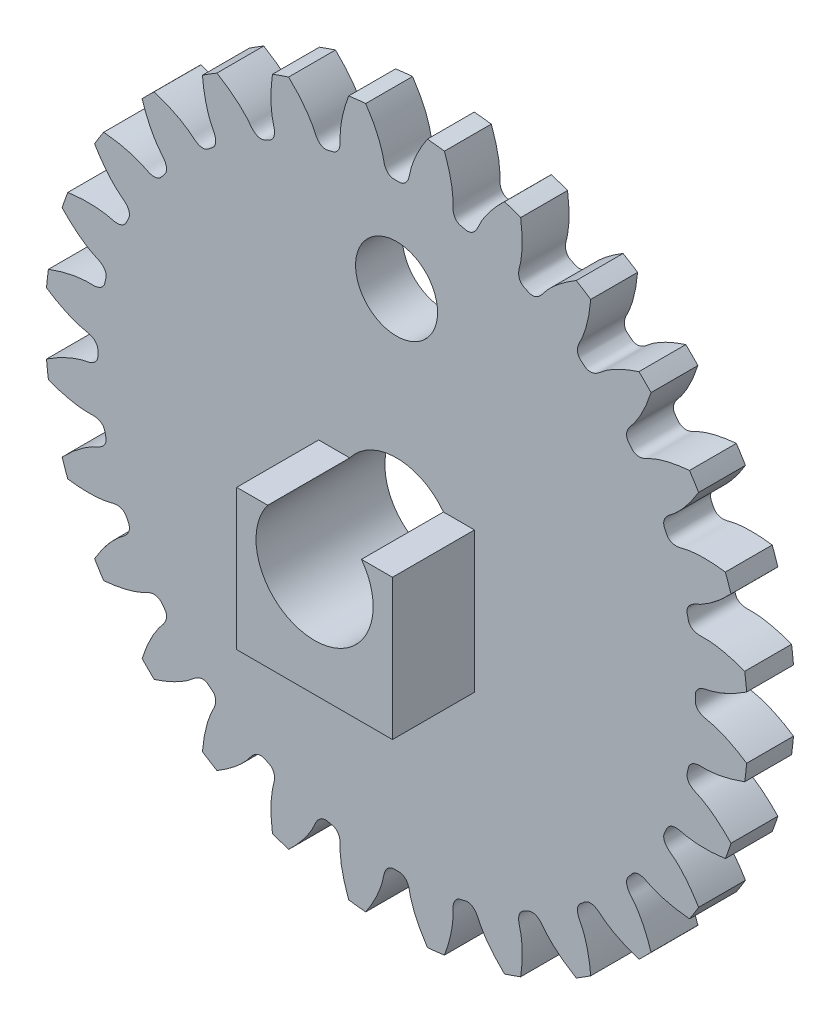
SolidWorks part; units mm, degrees
material "POM 乙缩醛共聚物"
ref_plane "前视基准面" through (0, 0, 0) normal (0, 0, 1) x (1, 0, 0)
ref_plane "上视基准面" through (0, 0, 0) normal (0, 1, 0) x (1, 0, 0)
ref_plane "右视基准面" through (0, 0, 0) normal (1, 0, 0) x (0, 0, -1)
ref_axis "基准轴1" through (0, 0, 55) along (0, 0, -1)
sketch "旋转草图小直齿轮" plane through (0, 0, 0) normal (1, 0, 0) x (0, 0, -1)
  line L0 (0, 0) -> (1, 0) construction
  line L1 (-2, 0) -> (-2, 30)
  line L2 (-2, 30) -> (2, 30)
  line L3 (2, 30) -> (2, 0)
  line L4 (2, 0) -> (-2, 0)
revolve "小直齿轮" add sketch "旋转草图小直齿轮" angle 360 about L0
sketch "齿草图小直齿轮" plane through (0, 0, 0) normal (0, 0, 1) x (1, 0, 0)
  arc A0 (29.9791, 2.6954) -> (29.9791, -2.6954) centre (0, 0) cw
  spline S0 degree 3 poles (29.9791, -2.6954) (29.8967, -2.6394) (29.7867, -2.5663) (29.6489, -2.4775) (29.568, -2.4262) (29.4879, -2.3761) (29.4084, -2.3272) (29.3297, -2.2795) (29.2518, -2.233) (29.1746, -2.1877) (29.0982, -2.1436) (29.0227, -2.1006) (28.9479, -2.0588) (28.8739, -2.0181) (28.8008, -1.9785) (28.7286, -1.94) (28.6572, -1.9027) (28.5866, -1.8664) (28.517, -1.8311) (28.4482, -1.7969) (28.3804, -1.7638) (28.3135, -1.7317) (28.2474, -1.7005) (28.1824, -1.6704) (28.1182, -1.6412) (28.0551, -1.6131) (27.9929, -1.5858) (27.9317, -1.5595) (27.8714, -1.5341) (27.8122, -1.5096) (27.754, -1.486) (27.6968, -1.4633) (27.6406, -1.4415) (27.5854, -1.4204) (27.5313, -1.4002) (27.4783, -1.3809) (27.4263, -1.3623) (27.3754, -1.3445) (27.3255, -1.3274) (27.2768, -1.3111) (27.2291, -1.2956) (27.1826, -1.2807) (27.1371, -1.2666) (27.0928, -1.2531) (27.0496, -1.2403) (27.0075, -1.2282) (26.9666, -1.2167) (26.9268, -1.2058) (26.8882, -1.1955) (26.8507, -1.1859) (26.8144, -1.1767) (26.7793, -1.1682) (26.7453, -1.1601) (26.7125, -1.1526) (26.6809, -1.1456) (26.6505, -1.1391) (26.6213, -1.133) (26.5933, -1.1274) (26.5665, -1.1222) (26.4964, -1.1093) (26.4158, -1.0949) (26.3261, -1.073) (26.2704, -1.0579) (26.2159, -1.0413) (26.1625, -1.0233) (26.1102, -1.0035) (26.0587, -0.9819) (26.0079, -0.9582) (25.9578, -0.9321) (25.9081, -0.9031) (25.8587, -0.8707) (25.8096, -0.8344) (25.7609, -0.7932) (25.7128, -0.7463) (25.6659, -0.6926) (25.6212, -0.6311) (25.5801, -0.5609) (25.5449, -0.4817) (25.5179, -0.3942) (25.5026, -0.3056) (25.4962, -0.1734) (25.5028, 0) (25.4962, 0.1734) (25.5026, 0.3056) (25.5179, 0.3942) (25.5449, 0.4817) (25.5801, 0.5609) (25.6212, 0.6311) (25.6659, 0.6926) (25.7128, 0.7463) (25.7609, 0.7932) (25.8096, 0.8344) (25.8587, 0.8707) (25.9081, 0.9031) (25.9578, 0.9321) (26.0079, 0.9582) (26.0587, 0.9819) (26.1102, 1.0035) (26.1625, 1.0233) (26.2159, 1.0413) (26.2704, 1.0579) (26.3261, 1.073) (26.4158, 1.0949) (26.4964, 1.1093) (26.5665, 1.1222) (26.5933, 1.1274) (26.6213, 1.133) (26.6505, 1.1391) (26.6809, 1.1456) (26.7125, 1.1526) (26.7453, 1.1601) (26.7793, 1.1682) (26.8144, 1.1767) (26.8507, 1.1859) (26.8882, 1.1955) (26.9268, 1.2058) (26.9666, 1.2167) (27.0075, 1.2282) (27.0496, 1.2403) (27.0928, 1.2531) (27.1371, 1.2666) (27.1826, 1.2807) (27.2291, 1.2956) (27.2768, 1.3111) (27.3255, 1.3274) (27.3754, 1.3445) (27.4263, 1.3623) (27.4783, 1.3809) (27.5313, 1.4002) (27.5854, 1.4204) (27.6406, 1.4415) (27.6968, 1.4633) (27.754, 1.486) (27.8122, 1.5096) (27.8714, 1.5341) (27.9317, 1.5595) (27.9929, 1.5858) (28.0551, 1.6131) (28.1182, 1.6412) (28.1824, 1.6704) (28.2474, 1.7005) (28.3135, 1.7317) (28.3804, 1.7638) (28.4482, 1.7969) (28.517, 1.8311) (28.5866, 1.8664) (28.6572, 1.9027) (28.7286, 1.94) (28.8008, 1.9785) (28.8739, 2.0181) (28.9479, 2.0588) (29.0227, 2.1006) (29.0982, 2.1436) (29.1746, 2.1877) (29.2518, 2.233) (29.3297, 2.2795) (29.4084, 2.3272) (29.4879, 2.3761) (29.568, 2.4262) (29.6489, 2.4775) (29.7867, 2.5663) (29.8967, 2.6394) (29.9791, 2.6954) knots 0 0 0 0 0.027017 0.035793 0.044454 0.053001 0.061433 0.06975 0.077952 0.08604 0.094013 0.101872 0.109615 0.117244 0.124758 0.132158 0.139443 0.146613 0.153668 0.160609 0.167434 0.174146 0.180742 0.187224 0.193591 0.199843 0.205981 0.212003 0.217912 0.223705 0.229384 0.234948 0.240397 0.245731 0.250951 0.256056 0.261046 0.265922 0.270683 0.275329 0.279861 0.284277 0.288579 0.292767 0.296839 0.300797 0.30464 0.308369 0.311982 0.315481 0.318866 0.322135 0.32529 0.32833 0.331255 0.334066 0.336762 0.339343 0.34181 0.344161 0.358685 0.363984 0.369197 0.374338 0.379423 0.384472 0.389509 0.39456 0.399659 0.404844 0.410158 0.415656 0.421394 0.427439 0.433855 0.440707 0.448038 0.455865 0.464152 0.472805 0.480182 0.5 0.519818 0.527195 0.535848 0.544135 0.551962 0.559293 0.566145 0.572561 0.578606 0.584344 0.589842 0.595156 0.600341 0.60544 0.610491 0.615528 0.620577 0.625662 0.630803 0.636016 0.641315 0.655839 0.65819 0.660657 0.663238 0.665934 0.668745 0.67167 0.67471 0.677865 0.681134 0.684519 0.688018 0.691631 0.69536 0.699203 0.703161 0.707233 0.711421 0.715723 0.720139 0.724671 0.729317 0.734078 0.738954 0.743944 0.749049 0.754269 0.759603 0.765052 0.770616 0.776295 0.782088 0.787997 0.794019 0.800157 0.806409 0.812776 0.819258 0.825854 0.832566 0.839391 0.846332 0.853387 0.860557 0.867842 0.875242 0.882756 0.890385 0.898128 0.905987 0.91396 0.922048 0.93025 0.938567 0.946999 0.955546 0.964207 0.972983 1 1 1 1
extrude "齿拉伸切除小直齿轮" cut sketch "齿草图小直齿轮" against normal blind 2 and the other way blind 2
pattern_circular "齿形小直齿轮" count 28 every 12.857 about axis through (0, 0, 55) along (0, 0, -1) of "齿拉伸切除小直齿轮"
sketch "辅助草图小直齿轮" plane through (0, 0, 0) normal (0, 0, 1) x (1, 0, 0)
  circle A0 centre (0, 0) radius 28 construction
  circle A1 centre (0, 0) radius 26.3114 construction
  circle A2 centre (0, 0) radius 26.5329 construction
  circle A3 centre (0, 0) radius 30 construction
  circle A4 centre (0, 0) radius 25.5 construction
  dimension "PitchDiameter" = 56
  dimension "BaseDiameter" = 52.6228
  dimension "FormDiameter" = 53.0658
  dimension "MajorDiameter" = 60
  dimension "MinorDiameter" = 51
sketch "草图1" plane through (0, 0, 2) normal (0, 0, 1) x (1, 0, 0)
  circle A0 centre (0, 0) radius 5
  circle A1 centre (0, 17.5) radius 3.5
  dimension "D2" = 7
  dimension "D3" = 10
  dimension "D1" = 17.5
extrude "切除-拉伸1" cut sketch "草图1" against normal blind 10
sketch "草图2" plane through (0, 0, 2) normal (0, 0, 1) x (1, 0, 0)
  line L0 (-6.65, 3) -> (6.65, 3)
  line L1 (-6.65, 3) -> (-6.65, -9)
  line L2 (-6.65, -9) -> (6.65, -9)
  line L3 (6.65, -9) -> (6.65, 3)
  line L4 (0, 0) -> (0, 13.5324) construction
  circle A0 centre (0, 0) radius 5 construction
  circle A1 centre (0, 0) radius 5
  dimension "D1" = 3
  dimension "D2" = 12
  dimension "D3" = 13.3
extrude "凸台-拉伸1" add sketch "草图2" along normal blind 7 contours A1 L0 L1 L2 L3 region at (-5.325, 2.8209, 2)
